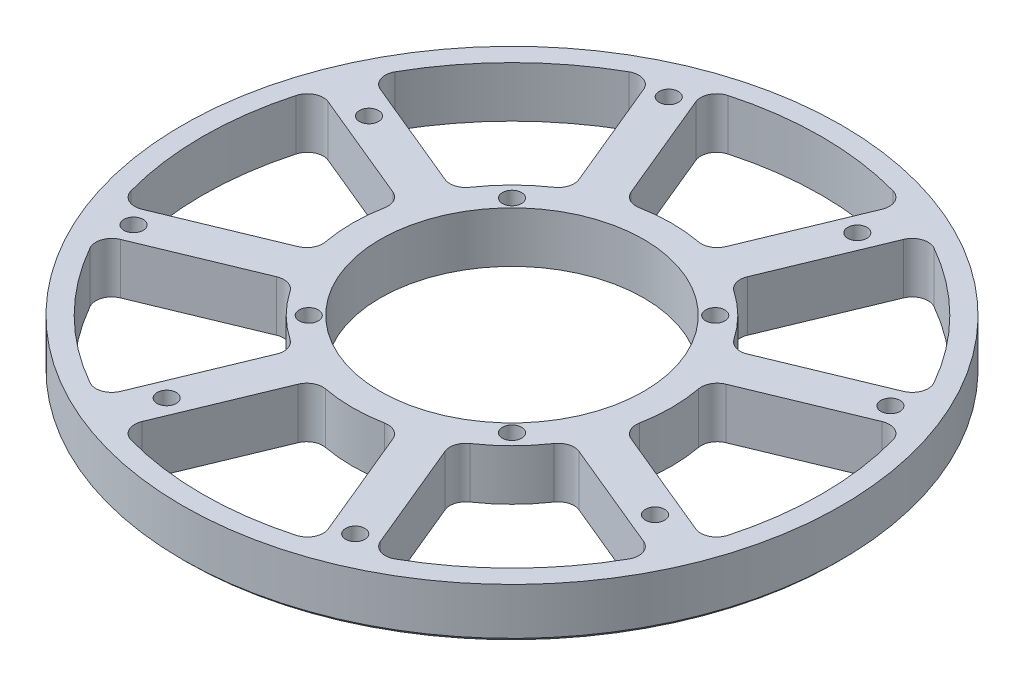
SolidWorks part; units mm, degrees
material "6061-T6 (SS)"
ref_plane "Front Plane" through (0, 0, 0) normal (0, 0, 1) x (1, 0, 0)
ref_plane "Top Plane" through (0, 0, 0) normal (0, 1, 0) x (1, 0, 0)
ref_plane "Right Plane" through (0, 0, 0) normal (1, 0, 0) x (0, 0, -1)
sketch "Sketch2" plane through (0, 0, 0) normal (1, 0, 0) x (0, 0, -1)
  line L0 (0, 0) -> (-82.55, 0)
  line L1 (-82.55, 0) -> (-82.55, 12.7)
  line L2 (-82.55, 12.7) -> (0, 12.7)
  line L5 (0, 12.7) -> (0, 0)
  dimension "D1" = 82.55
  dimension "D2" = 12.7
ref_axis "Axis1" through (0, -0.635, 0) along (0, 1, 0)
revolve "Revolve1" add sketch "Sketch2" angle 360 about axis through (0, -0.635, 0) along (0, 1, 0)
hole_wizard "#12 (0.189) Diameter Hole1" positions "Sketch6" profile "Sketch7" hole size "#12" standard "ANSI Inch" end condition through all
sketch "Sketch6" plane through (0, 12.7, 0) normal (0, 1, 0) x (1, 0, 0)
  line L0 (0, 0) -> (-53.438, 129.0108) construction
  line L2 (0, 0) -> (0, 109.0908) construction
  line L3 (0, 0) -> (-76.2663, 31.5905) construction
  line L4 (0, 0) -> (-68.4315, 68.4315) construction
  circle A0 centre (0, 0) radius 82.55 construction
  point P0 (-27.7637, 67.0275)
  point P18 (-61.1608, 25.3336)
  point P27 (-25.4558, 25.4558)
  dimension "D1" = 22.5
  dimension "D2" = 72.55
  dimension "D3" = 45
  dimension "D4" = 66.2
  dimension "D6" = 22.5
  dimension "D5" = 36
sketch "Sketch7" plane through (-27.7637, 12.7, -67.0275) normal (1, 0, 0) x (0, 0, 1)
  line L0 (0, 0) -> (0, 12.7)
  line L1 (0, 12.7) -> (2.4003, 12.7)
  line L2 (2.4003, 12.7) -> (2.4003, 0)
  line L5 (2.4003, 0) -> (0, 0)
  line L11 (0, -6.35) -> (0, 107.95) construction
  dimension "Thru Hole Dia." = 4.8006
  dimension "Thru Hole Depth" = 12.7
pattern_circular "CirPattern3" count 4 over 360 about axis through (0, -0.635, 0) along (0, 1, 0) of "#12 (0.189) Diameter Hole1"
sketch "Sketch8" plane through (0, 12.7, 0) normal (0, 1, 0) x (1, 0, 0)
  line L4 (0, 0) -> (0, 93.9995) construction
  line L5 (0, 0) -> (113.8372, 0) construction
  line L6 (-10.5679, 38.5787) -> (-24.996, 73.4112)
  line L7 (10.5679, 38.5787) -> (24.996, 73.4112)
  line L8 (0, 0) -> (-27.7637, 67.0275) construction
  arc A0 (-10.5679, 38.5787) -> (10.5679, 38.5787) centre (0, 0) cw
  arc A1 (-24.996, 73.4112) -> (24.996, 73.4112) centre (0, 0) cw
  circle A2 centre (0, 0) radius 82.55 construction
  dimension "D1" = 40
  dimension "D2" = 5
  dimension "D3" = 5
extrude "Cut-Extrude1" cut sketch "Sketch8" against normal through all
fillet "Fillet1" radius 4 4 edges at (10.5679, 6.35, -38.5787) (24.996, 6.35, -73.4112) (-10.5679, 6.35, -38.5787) (-24.996, 6.35, -73.4112)
pattern_circular "CirPattern4" count 8 over 360 about axis through (0, -0.635, 0) along (0, 1, 0) of "Cut-Extrude1", "Fillet1"
chamfer "Chamfer2" distance 1 angle 45 1 edges at (0, 0, -82.55)
sketch "Sketch9" plane through (0, 12.7, 0) normal (0, 1, 0) x (1, 0, 0)
  circle A0 centre (0, 0) radius 33
  dimension "D1" = 66
extrude "Cut-Extrude2" cut sketch "Sketch9" against normal through all
equation "\"TubeDiameter\" = 6.500in"
equation "\"D1@Sketch2\"=\"TubeDiameter\"/2"
equation "\"D2@Sketch6\"=\"TubeDiameter\"/2-10mm"
